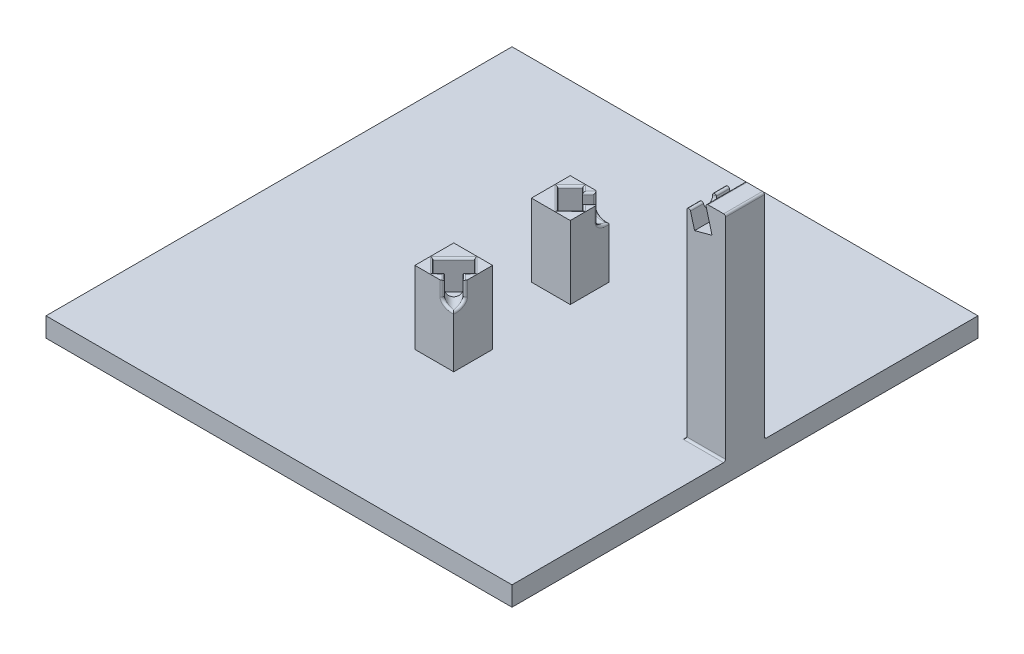
SolidWorks part; units mm, degrees
ref_plane "Front Plane" through (0, 0, 0) normal (0, 0, 1) x (1, 0, 0)
ref_plane "Top Plane" through (0, 0, 0) normal (0, 1, 0) x (1, 0, 0)
ref_plane "Right Plane" through (0, 0, 0) normal (1, 0, 0) x (0, 0, -1)
sketch "Sketch1" plane through (0, 0, 0) normal (0, 1, 0) x (1, 0, 0)
  line L1 (-304.8, 304.8) -> (304.8, 304.8)
  line L2 (-304.8, 304.8) -> (-304.8, -304.8)
  line L3 (-304.8, -304.8) -> (304.8, -304.8)
  line L4 (304.8, 304.8) -> (304.8, -304.8)
  point P4 (0, 304.8)
  point P8 (769.2167, -337.063)
  dimension "D1" = 304.8
  dimension "D2" = 304.8
  dimension "D3" = 609.6
  dimension "D4" = 609.6
extrude "Boss-Extrude1" add sketch "Sketch1" along normal blind 25.4
sketch "Sketch2" plane through (0, 25.4, 0) normal (0, 1, 0) x (1, 0, 0)
  line L1 (254, -25.4) -> (304.8, -25.4)
  line L2 (254, -25.4) -> (254, 25.4)
  line L3 (254, 25.4) -> (304.8, 25.4)
  line L4 (304.8, -25.4) -> (304.8, 25.4)
  line L5 (304.8, -304.8) -> (304.8, 304.8) construction
  line L6 (304.8, 304.8) -> (-304.8, 304.8) construction
  dimension "D1" = 50.8
  dimension "D2" = 50.8
  dimension "D3" = 279.4
extrude "Boss-Extrude2" add sketch "Sketch2" along normal blind 279.4
sketch "Sketch4" plane through (0, 0, 25.4) normal (0, 0, 1) x (1, 0, 0)
  line L0 (254, 304.8) -> (264.2089, 266.7)
  line L1 (254, 304.8) -> (276.86, 310.9253)
  line L2 (276.86, 310.9253) -> (287.0689, 272.8253)
  line L3 (287.0689, 272.8253) -> (264.2089, 266.7)
  line L4 (254, 304.8) -> (254, 25.4) construction
  dimension "D1" = 22.86
  dimension "D2" = 38.1
  dimension "D3" = 15
extrude "Cut-Extrude1" cut sketch "Sketch4" against normal blind 50.8
sketch "Sketch6" plane through (313.1852, 83.9177, 0) normal (0.9659, 0.2588, 0) x (0, 0, -1)
  line L0 (25.4, 228.6742) -> (-25.4, 228.6742) construction
  line L2 (25.4, 228.6742) -> (25.4, 189.2301) construction
  line L3 (-8.509, 209.6242) -> (-8.509, 228.6742)
  line L4 (-8.509, 228.6742) -> (8.509, 228.6742)
  line L5 (8.509, 228.6742) -> (8.509, 209.6242)
  arc A0 (-8.509, 209.6242) -> (8.509, 209.6242) centre (0, 209.6242) ccw
  dimension "D2" = 17.018
  dimension "D1" = 19.05
  dimension "D3" = 25.4
extrude "Cut-Extrude2" cut sketch "Sketch6" against normal blind 12.7
fillet "Fillet6" radius 2.54 3 edges at (279.4, 25.4, 25.4) (254, 25.4, 0) (279.4, 25.4, -25.4)
fillet "Fillet7" radius 2.54 4 edges at (304.8, 304.8, 0) (278.5013, 304.8, 0) (254, 304.8, 16.9545) (254, 304.8, -16.9545)
sketch "Sketch11" plane through (0, 25.4, 0) normal (0, 1, 0) x (1, 0, 0)
  line L0 (304.8, 304.8) -> (-304.8, 304.8) construction
  line L1 (-25.4, 101.6) -> (25.4, 101.6)
  line L2 (-25.4, 101.6) -> (-25.4, 50.8)
  line L3 (-25.4, 50.8) -> (25.4, 50.8)
  line L4 (25.4, 101.6) -> (25.4, 50.8)
  line L5 (304.8, 27.94) -> (304.8, 304.8) construction
  line L6 (304.8, -304.8) -> (304.8, -27.94) construction
  line L7 (-25.4, -50.8) -> (25.4, -50.8)
  line L8 (-25.4, -50.8) -> (-25.4, -101.6)
  line L9 (-25.4, -101.6) -> (25.4, -101.6)
  line L10 (25.4, -50.8) -> (25.4, -101.6)
  line L11 (-304.8, -304.8) -> (304.8, -304.8) construction
  dimension "D1" = 50.8
  dimension "D2" = 50.8
  dimension "D3" = 203.2
  dimension "D4" = 279.4
  dimension "D5" = 50.8
  dimension "D6" = 50.8
  dimension "D7" = 279.4
  dimension "D8" = 203.2
extrude "Boss-Extrude5" add sketch "Sketch11" along normal blind 95.25
sketch "Sketch12" plane through (0, 120.65, 0) normal (0, 1, 0) x (1, 0, 0)
  line L0 (-25.4, -101.6) -> (25.4, -50.8)
  line L10 (-5.3882, -97.7526) -> (21.5526, -70.8118)
  line L11 (-25.4, -101.6) -> (25.4, -101.6) construction
  line L12 (-5.3882, -97.7526) -> (-21.5526, -81.5882)
  line L13 (-21.5526, -81.5882) -> (5.3882, -54.6474)
  line L14 (5.3882, -54.6474) -> (21.5526, -70.8118)
  line L15 (25.4, -101.6) -> (25.4, -50.8) construction
  line L16 (-25.4, -50.8) -> (25.4, -101.6)
  dimension "D1" = 38.1
  dimension "D2" = 45
  dimension "D3" = 11.43
  dimension "D4" = 22.86
  dimension "D5" = 19.05
  dimension "D6" = 90
extrude "Cut-Extrude11" cut sketch "Sketch12" against normal blind 38.1 contours L16 L0 L12 L10 | L16 L13 L12 L0 | L13 L16 L0 L14 | L0 L16 L10 L14 region at (-10.7763, 120.65, 78.8941) region at (-2.6941, 120.65, 86.9763) region at (2.6941, 120.65, 65.4237) region at (10.7763, 120.65, 73.5059)
sketch "Sketch13" plane through (46.1822, 0, 46.1822) normal (-0.7071, 0, -0.7071) x (-0.7071, 0, 0.7071)
  line L0 (72.9315, 120.65) -> (34.8315, 120.65) construction
  line L1 (34.8315, 82.55) -> (34.8315, 120.65) construction
  line L2 (62.3905, 101.6) -> (62.3905, 120.65)
  line L3 (62.3905, 120.65) -> (45.3725, 120.65)
  line L4 (45.3725, 120.65) -> (45.3725, 101.6)
  arc A0 (45.3725, 101.6) -> (62.3905, 101.6) centre (53.8815, 101.6) ccw
  dimension "D1" = 17.018
  dimension "D2" = 19.05
  dimension "D3" = 19.05
extrude "Cut-Extrude12" cut sketch "Sketch13" against normal blind 38.1
fillet "Fillet8" radius 2.54 11 edges at (7.716, 120.65, 95.9495) (19.7495, 120.65, 83.916) (17.8258, 120.65, 74.5387) (-1.6613, 120.65, 94.0258) (-13.4704, 120.65, 89.6704) (-8.0822, 120.65, 68.1178) (13.4704, 120.65, 62.7296) (25.4, 111.125, 89.5665) (25.4, 95.5832, 93.091) (16.891, 95.5832, 101.6) (13.3665, 111.125, 101.6)
sketch "Sketch14" plane through (0, 120.65, 0) normal (0, 1, 0) x (1, 0, 0)
  line L0 (-5.3882, 97.7526) -> (21.5526, 70.8118)
  line L1 (21.5526, 70.8118) -> (5.3882, 54.6474)
  line L2 (5.3882, 54.6474) -> (-21.5526, 81.5882)
  line L3 (-21.5526, 81.5882) -> (-5.3882, 97.7526)
  line L4 (-25.4, 101.6) -> (25.4, 50.8)
  line L5 (25.4, 101.6) -> (-25.4, 50.8)
  line L7 (25.4, 101.6) -> (-25.4, 101.6) construction
  point P14 (-8.0822, 68.1178)
  point P15 (13.4704, 62.7296)
  dimension "D1" = 38.1
  dimension "D2" = 45
  dimension "D3" = 22.86
extrude "Cut-Extrude13" cut sketch "Sketch14" against normal blind 38.1 contours L5 L0 L3 L4 | L5 L4 L3 L2 | L4 L5 L2 L1 | L0 L5 L4 L1 region at (-2.6941, 120.65, -86.9763) region at (10.7763, 120.65, -73.5059) region at (-10.7763, 120.65, -78.8941) region at (2.6941, 120.65, -65.4237)
sketch "Sketch15" plane through (46.1822, 0, -46.1822) normal (-0.7071, 0, 0.7071) x (0.7071, 0, 0.7071)
  line L0 (-72.9315, 120.65) -> (-34.8315, 120.65) construction
  line L1 (-72.9315, 82.55) -> (-72.9315, 120.65) construction
  line L2 (-62.3905, 101.6) -> (-62.3905, 120.65)
  line L3 (-62.3905, 120.65) -> (-45.3725, 120.65)
  line L4 (-45.3725, 120.65) -> (-45.3725, 101.6)
  arc A0 (-62.3905, 101.6) -> (-45.3725, 101.6) centre (-53.8815, 101.6) ccw
  dimension "D1" = 17.018
  dimension "D2" = 19.05
  dimension "D3" = 19.05
extrude "Cut-Extrude15" cut sketch "Sketch15" against normal blind 38.1
fillet "Fillet9" radius 2.54 11 edges at (13.3665, 111.125, -101.6) (-1.6613, 120.65, -94.0258) (-13.4704, 120.65, -89.6704) (-8.0822, 120.65, -68.1178) (13.4704, 120.65, -62.7296) (17.8258, 120.65, -74.5387) (19.7495, 120.65, -83.916) (7.716, 120.65, -95.9495) (16.891, 95.5832, -101.6) (25.4, 111.125, -89.5665) (25.4, 95.5832, -93.091)
